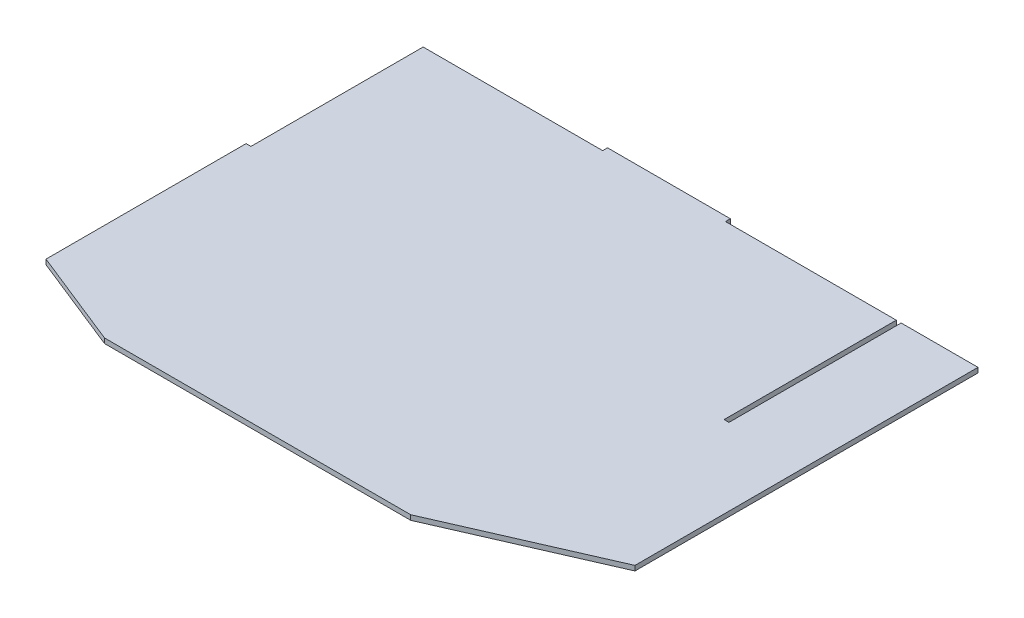
SolidWorks part; units mm, degrees
material "Custom Plastic"
ref_plane "X-Y Datum" through (0, 0, 0) normal (0, 0, 1) x (1, 0, 0)
ref_plane "X-Z Datum" through (0, 0, 0) normal (0, 1, 0) x (1, 0, 0)
ref_plane "Y-Z Datum" through (0, 0, 0) normal (1, 0, 0) x (0, 0, -1)
sketch "Sketch1" plane through (0, 0, 0) normal (0, 0, 1) x (1, 0, 0)
  line L1 (-154.051, -1.5875) -> (154.051, -1.5875)
  line L2 (-154.051, -1.5875) -> (-154.051, 1.5875)
  line L3 (-154.051, 1.5875) -> (154.051, 1.5875)
  line L4 (154.051, -1.5875) -> (154.051, 1.5875)
  line L5 (-154.051, -1.5875) -> (154.051, 1.5875) construction
  line L6 (-154.051, 1.5875) -> (154.051, -1.5875) construction
  point P0 (0, 0)
  dimension "D1" = 3.175
  dimension "D2" = 308.102
extrude "Boss-Extrude1" add sketch "Sketch1" along normal blind 267.83
sketch "Sketch3" plane through (154.051, 0, 0) normal (1, 0, 0) x (0, 0, -1)
  line L0 (-267.83, 1.5875) -> (0, 1.5875) construction
  line L1 (-267.83, -1.5875) -> (-112.128, -1.5875)
  line L2 (-267.83, -1.5875) -> (-267.83, 1.5875)
  line L3 (-267.83, 1.5875) -> (-112.128, 1.5875)
  line L4 (-112.128, -1.5875) -> (-112.128, 1.5875)
  dimension "D1" = 155.702
extrude "Boss-Extrude3" add sketch "Sketch3" along normal blind 3.175
mirror "Mirror1" about plane through (0, 0, 0) normal (1, 0, 0) of "Boss-Extrude3"
sketch "Sketch4" plane through (0, 0, 267.83) normal (0, 0, 1) x (1, 0, 0)
  line L1 (157.226, -1.5875) -> (207.264, -1.5875)
  line L2 (157.226, -1.5875) -> (157.226, 1.5875)
  line L3 (157.226, 1.5875) -> (207.264, 1.5875)
  line L4 (207.264, -1.5875) -> (207.264, 1.5875)
  dimension "D1" = 3.175
  dimension "D2" = 50.038
extrude "Boss-Extrude4" add sketch "Sketch4" against normal blind 267.83
sketch "Sketch6" plane through (0, 1.5875, 0) normal (0, 1, 0) x (1, 0, 0)
  line L0 (105.664, -267.83) -> (105.664, -223.38)
  line L1 (207.264, -267.83) -> (-157.226, -267.83) construction
  line L2 (207.264, -223.38) -> (105.664, -223.38)
  line L3 (207.264, 0) -> (207.264, -267.83) construction
  line L4 (105.664, -267.83) -> (207.264, -223.38)
  line M9 (-157.226, -267.83) -> (207.264, -267.83)
  line M10 (207.264, -267.83) -> (207.264, 0)
  dimension "D1" = 44.45
  dimension "D2" = 101.6
extrude "Cut-Extrude1" cut sketch "Sketch6" against normal through all contours L4 M9 M10 region at (173.3973, 1.5875, 253.0133)
sketch "Sketch7" plane through (0, -1.5875, 0) normal (0, -1, 0) x (1, 0, 0)
  line L0 (-93.726, 267.83) -> (-93.726, 242.43)
  line L1 (-157.226, 267.83) -> (105.664, 267.83) construction
  line L2 (-157.226, 242.43) -> (-93.726, 242.43)
  line L3 (-157.226, 267.83) -> (-157.226, 112.128) construction
  line L4 (-157.226, 242.43) -> (-93.726, 267.83)
  line M4 (105.664, 267.83) -> (-157.226, 267.83)
  line M5 (-157.226, 267.83) -> (-157.226, 112.128)
  dimension "D1" = 63.5
  dimension "D2" = 25.4
extrude "Cut-Extrude2" cut sketch "Sketch7" against normal through all contours L4 M5 M4 region at (-136.0593, -1.5875, 259.3633)
sketch "Sketch8" plane through (0, 0, 0) normal (0, 0, -1) x (-1, 0, 0)
  line L1 (37.169, 1.5875) -> (-42.831, 1.5875)
  line L2 (37.169, 1.5875) -> (37.169, -1.5875)
  line L3 (37.169, -1.5875) -> (-42.831, -1.5875)
  line L4 (-42.831, 1.5875) -> (-42.831, -1.5875)
extrude "Boss-Extrude6" add sketch "Sketch8" along normal blind 3.175
